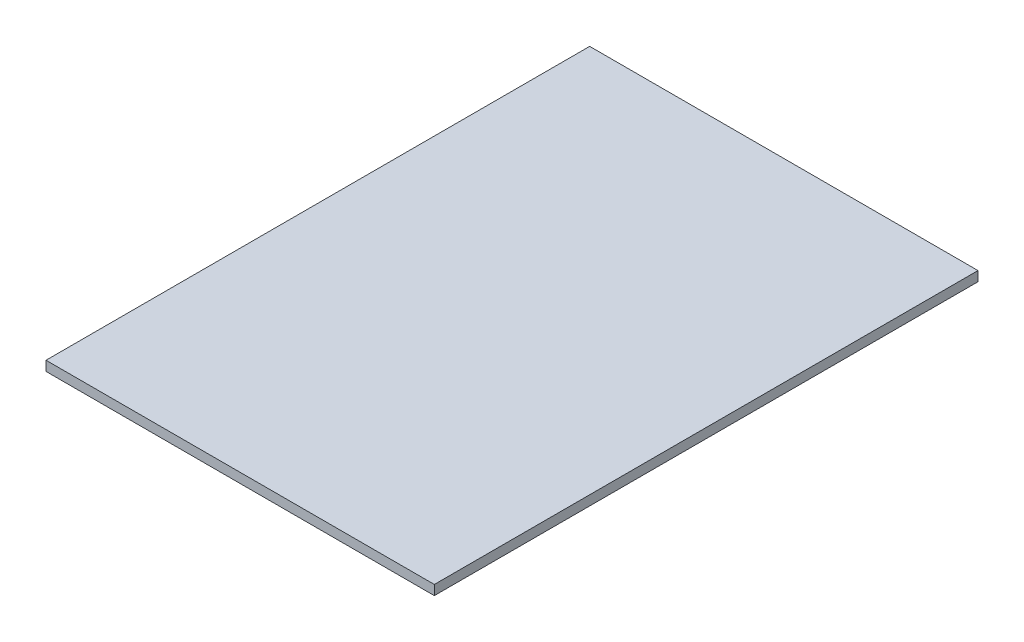
SolidWorks part; units mm, degrees
ref_plane "Front Plane" through (0, 0, 0) normal (0, 0, 1) x (1, 0, 0)
ref_plane "Top Plane" through (0, 0, 0) normal (0, 1, 0) x (1, 0, 0)
ref_plane "Right Plane" through (0, 0, 0) normal (1, 0, 0) x (0, 0, -1)
sketch "Sketch1" plane through (0, 0, 0) normal (0, 1, 0) x (1, 0, 0)
  line L0 (63.5, 177.8) -> (63.5, 0) construction
  line L1 (0, 0) -> (127, 0)
  line L2 (0, 0) -> (0, 177.8)
  line L3 (0, 177.8) -> (127, 177.8)
  line L4 (127, 0) -> (127, 177.8)
  line L9 (63.5, 139.7) -> (63.5, 116.7) construction
  dimension "D1" = 127
  dimension "D2" = 177.8
extrude "Boss-Extrude2" add sketch "Sketch1" along normal blind 3.175
ref_plane "Plane1" through (0, 0, -158.75) normal (0, 0, -1) x (-1, 0, 0)
sketch "Sketch5" plane through (0, 0, -158.75) normal (0, 0, -1) x (-1, 0, 0)
  line L0 (-127, 3.175) -> (0, 3.175) construction
  line L6 (-63.5, 3.175) -> (-63.5, 0) construction
  line L7 (-127, 0) -> (0, 0) construction
